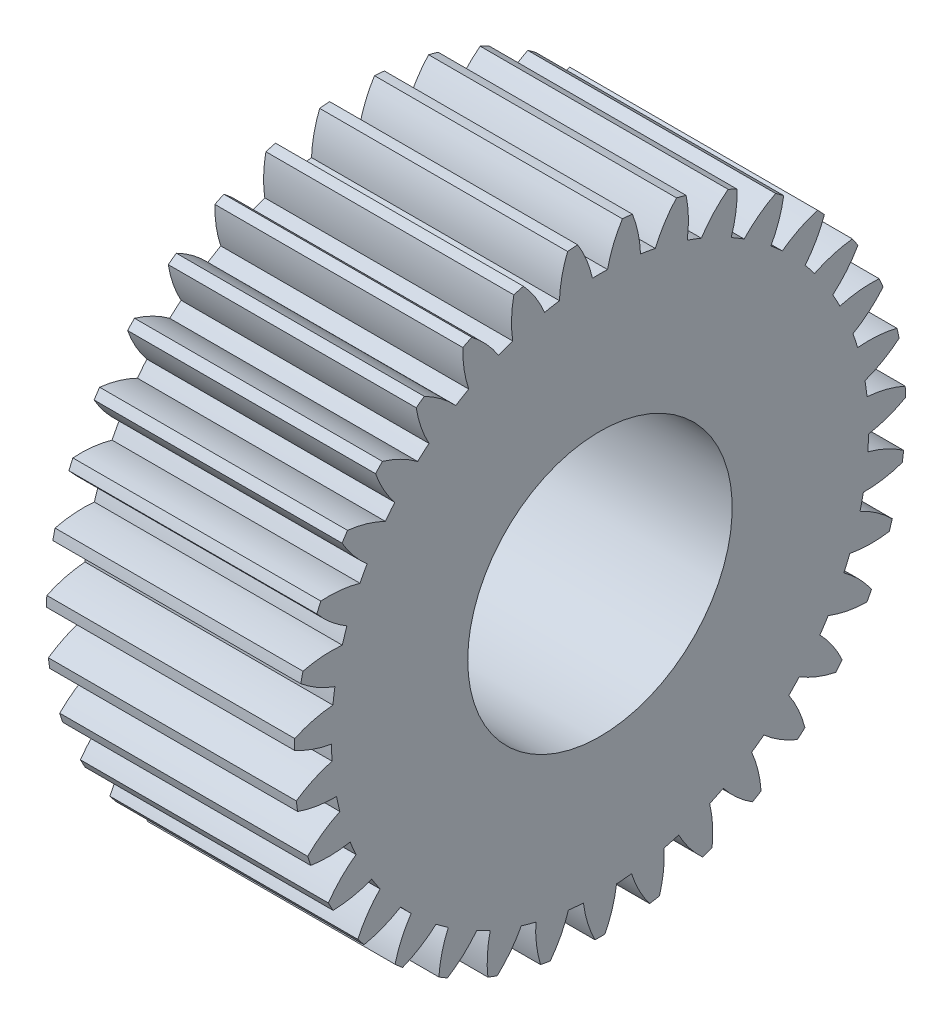
SolidWorks part; units mm, degrees
ref_plane "Plane1" through (0, 0, 0) normal (0, 0, 1) x (1, 0, 0)
ref_plane "Plane2" through (0, 0, 0) normal (0, 1, 0) x (1, 0, 0)
ref_plane "Plane3" through (0, 0, 0) normal (1, 0, 0) x (0, 0, -1)
sketch "HoldingSke" plane through (0, 0, 0) normal (0, 1, 0) x (1, 0, 0)
  line L0 (0, 0) -> (0.8192, -0.5736)
  line L1 (-15, 0) -> (100, 0) construction
  line L2 (0, 0) -> (-2.1039, 2.3779)
  line L3 (0, 0) -> (-11.863, 4.5341)
  line L4 (0, 0) -> (7.0742, 4.9534)
  line L5 (0, 0) -> (-46.8476, -17.4728)
  line L6 (0, 0) -> (-12.4344, -8.3896)
  line L7 (-2.1039, 2.3779) -> (8.6586, 51.2059)
  line L8 (-76.2, 54.61) -> (-73.9, 54.61)
  line L9 (-71.009, 38.7566) -> (-53.1078, 45.2721)
  line L10 (-76.2, 71.12) -> (104.1128, 71.12)
  line L11 (0, 0) -> (-15, 0)
  line L12 (-76.2, 101.6) -> (-76.162, 101.6)
  line L13 (24.9733, 27.94) -> (52.9518, 28.4284)
  line L14 (24.9733, 27.94) -> (24.9743, 27.94)
  line L15 (24.9733, 27.94) -> (100.4006, 29.5858)
  line L16 (-63.627, -1) -> (-12.827, -1)
  circle A0 centre (0, 0) radius 8
  circle A1 centre (0, 0) radius 16.249
  circle A2 centre (0, 0) radius 37.5
  circle A3 centre (0, 0) radius 8
  dimension "Num_teeth" = 35
  dimension "Pitch_radius" = 180.3128
  dimension "Width" = 15
  dimension "Thickness" = 15
sketch "BasProSke" plane through (0, 0, 0) normal (0, 1, 0) x (1, 0, 0)
  line L0 (-10, 0) -> (60, 0) construction
  line L1 (0, 0) -> (0, 18.5)
  line L2 (0, 0) -> (15, 0)
  line L3 (15, 0) -> (15, 18.5)
  line L4 (15, 18.5) -> (0, 18.5)
  dimension "Thickness" = 15
  dimension "Diameter" = 37
revolve "Base-Revolve" add sketch "BasProSke" angle 360 about L0
sketch "TooCutSke" plane through (0, 0, 0) normal (1, 0, 0) x (0, 0, -1)
  line L1 (0, 0) -> (0, 107) construction
  line L2 (0, 0) -> (-0.8516, 17.4793) construction
  line L3 (0, 0) -> (-3.1347, 34.8297) construction
  line L4 (-0.8516, 17.4793) -> (-1.5674, 17.4148) construction
  arc A0 (0.4564, 16.2426) -> (-0.4564, 16.2426) centre (0, 0) ccw
  arc A1 (1.373, 18.4745) -> (-1.373, 18.4745) centre (0, 0) ccw
  circle A2 centre (0, 0) radius 17.5 construction
  circle A3 centre (0, 0) radius 16.4446 construction
  arc A4 (-0.4564, 16.2426) -> (-1.373, 18.4745) centre (-7.293, 14.739) ccw
  arc A5 (1.373, 18.4745) -> (0.4564, 16.2426) centre (7.293, 14.739) ccw
extrude "ToothCut" cut sketch "TooCutSke" along normal through all
fillet "Breaks" [suppressed] radius 0.02 tangent propagation no
fillet "RootFillets" [suppressed] radius 0.251
pattern_circular "TeethCuts" count 35 every 10.286 about axis through (-10, 0, 0) along (1, 0, 0) of "ToothCut", "RootFillets", "Breaks"
sketch "HubNeaOneSke" plane through (0, 0, 0) normal (-1, 0, 0) x (0, 0, 1)
  circle A0 centre (0, 0) radius 16.249
  dimension "Diameter" = 32.498
extrude "HubNearOne" [suppressed] add sketch "HubNeaOneSke" along normal blind 35.0001
sketch "HubNeaBotSke" plane through (0, 0, 0) normal (-1, 0, 0) x (0, 0, 1)
  circle A0 centre (0, 0) radius 16.249
  dimension "Diameter" = 32.498
extrude "HubNearBoth" [suppressed] add sketch "HubNeaBotSke" along normal blind 17.5
ref_plane "FarPln" through (15, 0, 0) normal (1, 0, 0) x (0, 0, -1)
sketch "HubFarSke" plane through (15, 0, 0) normal (1, 0, 0) x (0, 0, -1)
  circle A0 centre (0, 0) radius 16.249
  dimension "Diameter" = 32.498
extrude "HubFar" [suppressed] add sketch "HubFarSke" along normal blind 17.5
sketch "BorSke" plane through (0, 0, 0) normal (1, 0, 0) x (0, 0, -1)
  circle A0 centre (0, 0) radius 8
  dimension "Diameter" = 16
extrude "Bore" cut sketch "BorSke" along normal mid plane 100.0001
sketch "KeySke" plane through (0, 0, 0) normal (1, 0, 0) x (0, 0, -1)
  line L0 (-2.5, 0) -> (-2.5, 10.3)
  line L1 (-2.5, 10.3) -> (2.5, 10.3)
  line L2 (2.5, 10.3) -> (2.5, 0)
  line L3 (0, 0) -> (0, 34) construction
  line L4 (-2.5, 0) -> (2.5, 0)
  dimension "Width" = 5
extrude "Keyway" [suppressed] cut sketch "KeySke" along normal mid plane 100.0001
pattern_circular "Keyway2" [suppressed] count 2 every 90 about axis through (-10, 0, 0) along (1, 0, 0) reverse direction yes
equation "' \"Module@HoldingSke\" = 6.35"
equation "' \"Num_teeth@HoldingSke\" = 12"
equation "' \"Ap@HoldingSke\" =  20"
equation "' \"Ap@HoldingSke\" = 20"
equation "' \"Width@HoldingSke\" = 0.5 * 25.4"
equation "' \"Hub_dia@HoldingSke\"= 1 * 25.4"
equation "' \"Hub_dia@HoldingSke\" = 1 * 25.4"
equation "' \"Overall_len@HoldingSke\" = 1.0 * 25.4"
equation "' \"Bore@HoldingSke\" = 0.75 * 25.4"
equation "' \"T_dim@HoldingSke\" = 0.1 * 25.4"
equation "' \"Width@KeySke\" = 0.25 * 25.4"
equation "' \"Show_teeth@HoldingSke\" = 13"
equation "' \"Backlash@HoldingSke\" = 0.009 * 25.4"
equation "' \"Addendum_fac@HoldingSke\" = 1.0"
equation "' \"Dedendum_fac@HoldingSke\" = 1.25"
equation "' \"Dedendum_add@HoldingSke\" = 0.00005 * 25.4"
equation "' \"Clearance_fac@HoldingSke\" = 0.25"
equation "\"Pitch@HoldingSke\" = 1 / \"Module@HoldingSke\""
equation "\"Overcut_dia@TooCutSke\" = (\"Num_teeth@HoldingSke\" + 2 * \"Addendum_fac@HoldingSke\") / \"Pitch@HoldingSke\" + 0.002 * 25.4"
equation "\"Pitch_dia@TooCutSke\" = \"Num_teeth@HoldingSke\" / \"Pitch@HoldingSke\""
equation "\"Base_dia@TooCutSke\" = \"Num_teeth@HoldingSke\" / \"Pitch@HoldingSke\" * cos((\"Ap@HoldingSke\"  * 3.14159265 / 180))"
equation "\"Root_dia@TooCutSke\" = (\"Num_teeth@HoldingSke\" + 2) / \"Pitch@HoldingSke\" - 2 * (\"Addendum_fac@HoldingSke\" + \"Dedendum_fac@HoldingSke\") / \"Pitch@HoldingSke\" - \"Dedendum_add@HoldingSke\" * 2"
equation "\"Half_ang@TooCutSke\" = 180 / \"Num_teeth@HoldingSke\""
equation "\"Half_CT@TooCutSke\" = \"Num_teeth@HoldingSke\" / \"Pitch@HoldingSke\" * sin((3.14159265 / 2 / \"Num_teeth@HoldingSke\")) / 2 - 7 * \"Backlash@HoldingSke\" / 4"
equation "\"Flank_rad@TooCutSke\" = \"Num_teeth@HoldingSke\" / \"Pitch@HoldingSke\" / 5"
equation "\"Radius@RootFillets\" = \"Clearance_fac@HoldingSke\" / \"Pitch@HoldingSke\" + \"Dedendum_add@HoldingSke\""
equation "\"Break_rad@Breaks\" = 0.02 / \"Pitch@HoldingSke\""
equation "\"Thickness@HoldingSke\" = \"Width@HoldingSke\""
equation "\"OAL@HoldingSke\" = \"Thickness@HoldingSke\""
equation "\"MHD@HoldingSke\" = (\"Num_teeth@HoldingSke\" + 2) / \"Pitch@HoldingSke\" - 2 * (\"Addendum_fac@HoldingSke\" + \"Dedendum_fac@HoldingSke\")  / \"Pitch@HoldingSke\" - \"Dedendum_add@HoldingSke\" * 2"
equation "\"MBD@HoldingSke\" = (\"Num_teeth@HoldingSke\" + 2) / \"Pitch@HoldingSke\" - 2 * (\"Addendum_fac@HoldingSke\" + \"Dedendum_fac@HoldingSke\")  / \"Pitch@HoldingSke\" - \"Dedendum_add@HoldingSke\" * 2 - 0.002 * 25.4"
equation "\"MHD@HoldingSke\" = ((sgn( \"MHD@HoldingSke\" - \"Hub_dia@HoldingSke\" )-1)*( \"MHD@HoldingSke\" - \"Hub_dia@HoldingSke\" ))/-2+ \"Hub_dia@HoldingSke\""
equation "\"MBD@HoldingSke\" = ((sgn( \"MBD@HoldingSke\" - \"Bore@HoldingSke\" )-1)*( \"MBD@HoldingSke\" - \"Bore@HoldingSke\" ))/-2+ \"Bore@HoldingSke\""
equation "\"OAL@HoldingSke\" = ((sgn( \"OAL@HoldingSke\" - \"Overall_len@HoldingSke\" )+1)*( \"OAL@HoldingSke\" - \"Overall_len@HoldingSke\" ))/2 + \"Overall_len@HoldingSke\" + 0.000002 * 25.4"
equation "\"Num_teeth@TeethCuts\" = int( \"Show_teeth@HoldingSke\" ) + 1"
equation "\"Num_teeth@TeethCuts\" = ((sgn( \"Num_teeth@TeethCuts\" - \"Num_teeth@HoldingSke\" )-1)*( \"Num_teeth@TeethCuts\" - \"Num_teeth@HoldingSke\" ))/-2+ \"Num_teeth@HoldingSke\""
equation "\"Num_teeth@TeethCuts\" = ((sgn( \"Num_teeth@TeethCuts\" - 2.0)+1)*( \"Num_teeth@TeethCuts\" - 2.0))/2 +2.0"
equation "\"Angle@TeethCuts\" = 360.0 / \"Num_teeth@HoldingSke\""
equation "\"Diameter@BasProSke\" = (\"Num_teeth@HoldingSke\" + 2 * \"Addendum_fac@HoldingSke\") / \"Pitch@HoldingSke\""
equation "\"Thickness@BasProSke\"  = \"Thickness@HoldingSke\""
equation "' \"Fillet_rad@BasProSke\" =  \"Thickness@HoldingSke\" * 0.05"
equation "' \"Fillet_rad@BasProSke\" = \"Thickness@HoldingSke\" * 0.05"
equation "\"MHD@HoldingSke\" = ((sgn( \"MHD@HoldingSke\" - \"Root_dia@TooCutSke\" )-1)*( \"MHD@HoldingSke\" - \"Root_dia@TooCutSke\" ))/-2+ \"Root_dia@TooCutSke\""
equation "\"Diameter@HubNeaOneSke\" = \"MHD@HoldingSke\""
equation "\"Length@HubNearOne\" = \"OAL@HoldingSke\" - \"Thickness@BasProSke\""
equation "\"Diameter@HubNeaBotSke\" = \"MHD@HoldingSke\""
equation "\"Length@HubNearBoth\" = ( \"OAL@HoldingSke\" - \"Thickness@BasProSke\" ) / 2.0"
equation "\"Thickness@FarPln\" = \"Thickness@BasProSke\""
equation "\"Diameter@HubFarSke\" = \"MHD@HoldingSke\""
equation "\"Length@HubFar\" = ( \"OAL@HoldingSke\" - \"Thickness@BasProSke\" ) / 2.0"
equation "\"Diameter@BorSke\" = \"MBD@HoldingSke\""
equation "\"D1@Bore\" = \"OAL@HoldingSke\" * 2.0"
equation "\"D1@Keyway\" = \"OAL@HoldingSke\" * 2.0"
equation "\"Offset@KeySke\" = \"T_dim@HoldingSke\" + \"MBD@HoldingSke\" / 2.0"
